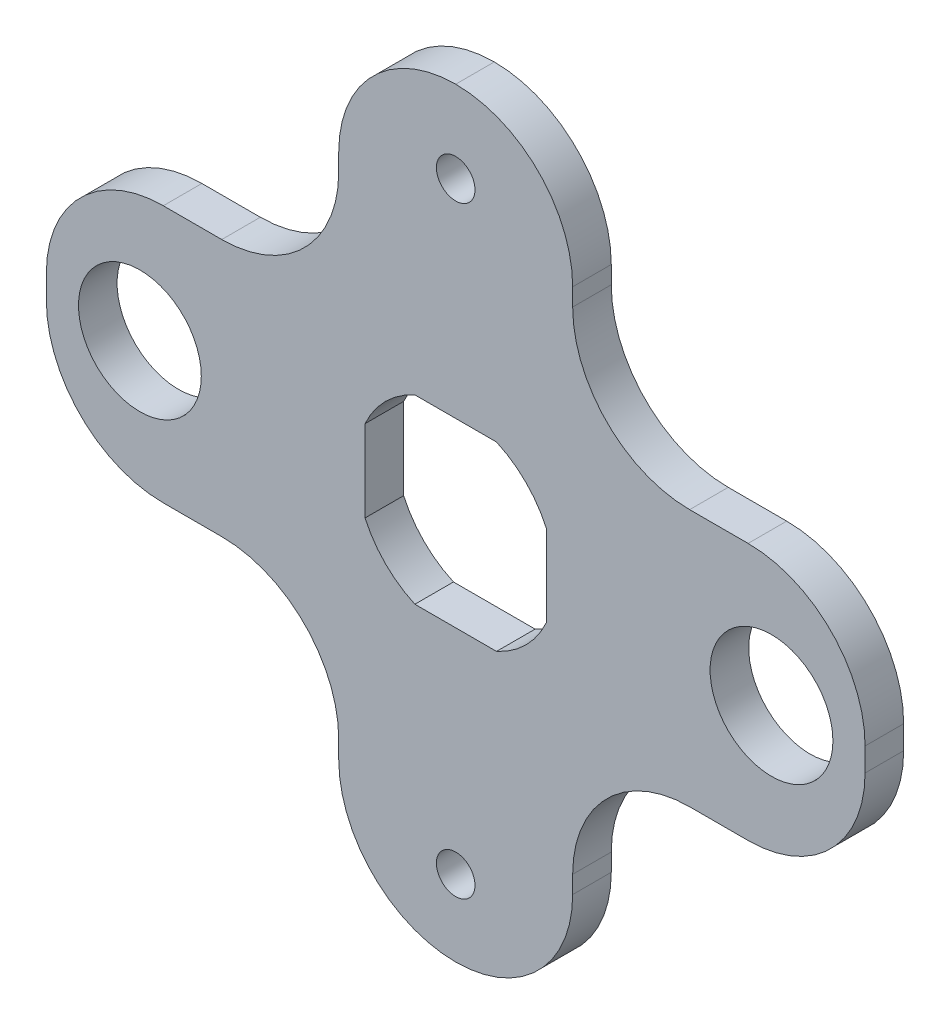
SolidWorks part; units mm, degrees
material "Thornel Mat VMA"
ref_plane "前视基准面" through (0, 0, 0) normal (0, 0, 1) x (1, 0, 0)
ref_plane "上视基准面" through (0, 0, 0) normal (0, 1, 0) x (1, 0, 0)
ref_plane "右视基准面" through (0, 0, 0) normal (1, 0, 0) x (0, 0, -1)
sketch "草图1" plane through (0, 0, 0) normal (0, 0, 1) x (1, 0, 0)
  line L0 (7.75, 0) -> (7.75, 15.5) construction
  line L1 (4.2589, 0) -> (11.2411, 0)
  line L2 (0, 4.2589) -> (0, 11.2411)
  line L3 (4.2589, 15.5) -> (11.2411, 15.5)
  line L4 (15.5, 4.2589) -> (15.5, 11.2411)
  line L5 (0, 7.75) -> (15.5, 7.75) construction
  line L6 (-27.25, -3.25) -> (-27.25, 18.75)
  line L7 (-27.25, 18.75) -> (-2.25, 18.75)
  line L8 (-2.25, 18.75) -> (-2.25, 40.25)
  line L9 (-2.25, 40.25) -> (17.75, 40.25)
  line L10 (17.75, 40.25) -> (17.75, 18.75)
  line L11 (17.75, 18.75) -> (42.75, 18.75)
  line L12 (42.75, 18.75) -> (42.75, -3.25)
  line L13 (42.75, -3.25) -> (17.75, -3.25)
  line L14 (17.75, -3.25) -> (17.75, -24.75)
  line L15 (17.75, -24.75) -> (-2.25, -24.75)
  line L16 (-2.25, -24.75) -> (-2.25, -3.25)
  line L17 (-2.25, -3.25) -> (-27.25, -3.25)
  arc A0 (4.2589, 15.5) -> (0, 11.2411) centre (7.75, 7.75) ccw
  arc A1 (11.2411, 0) -> (15.5, 4.2589) centre (7.75, 7.75) ccw
  circle A2 centre (34.75, 7.75) radius 5.25
  circle A3 centre (-19.25, 7.75) radius 5.25
  circle A4 centre (7.75, 33.25) radius 1.65
  circle A5 centre (7.75, -18.25) radius 1.65
  arc A6 (0, 4.2589) -> (4.2589, 0) centre (7.75, 7.75) ccw
  arc A7 (15.5, 11.2411) -> (11.2411, 15.5) centre (7.75, 7.75) ccw
  point P34 (0, 0)
  dimension "D2" = 10.5
  dimension "D1" = 10.5
  dimension "D3" = 27
  dimension "D4" = 27
  dimension "D5" = 26
  dimension "D6" = 25.5
  dimension "D7" = 3.3
  dimension "D8" = 3.3
  dimension "D9" = 70
  dimension "D10" = 65
  dimension "D11" = 22
  dimension "D12" = 20
extrude "凸台-拉伸1" add sketch "草图1" along normal blind 3.3 contours L17 L16 L15 L14 L13 L12 L11 L10 L9 L8 L7 L6 A5 A4 A3 A2 A1 L1 A0 L3 region at (-26.2948, 7.75, 0)
fillet "圆角1" radius 10 12 edges at (-27.25, 18.75, 1.65) (-27.25, -3.25, 1.65) (-2.25, -3.25, 1.65) (-2.25, -24.75, 1.65) (17.75, -24.75, 1.65) (17.75, -3.25, 1.65) (42.75, -3.25, 1.65) (42.75, 18.75, 1.65) (17.75, 18.75, 1.65) (-2.25, 18.75, 1.65) (-2.25, 40.25, 1.65) (17.75, 40.25, 1.65)
